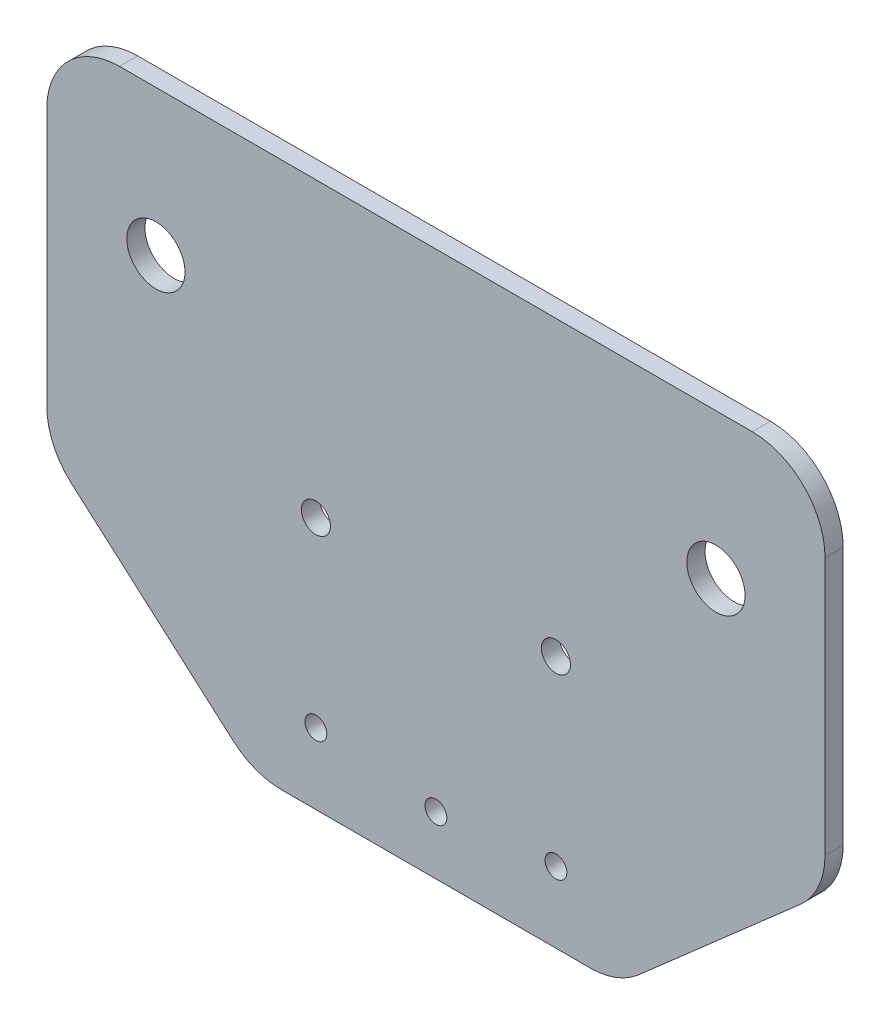
SolidWorks part; units mm, degrees
material "Maple"
ref_plane "Front Plane" through (0, 0, 0) normal (0, 0, 1) x (1, 0, 0)
ref_plane "Top Plane" through (0, 0, 0) normal (0, 1, 0) x (1, 0, 0)
ref_plane "Right Plane" through (0, 0, 0) normal (1, 0, 0) x (0, 0, -1)
sketch "Sketch1" plane through (0, 0, 0) normal (0, 0, 1) x (1, 0, 0)
  line L0 (53.5, 37.5) -> (-53.5, 37.5)
  line L1 (-53.5, -37.5) -> (53.5, -37.5) construction
  line L2 (-53.5, -37.5) -> (-53.5, 37.5) construction
  line L3 (-53.5, 37.5) -> (53.5, 37.5) construction
  line L4 (53.5, -37.5) -> (53.5, 37.5) construction
  line L5 (-53.5, -37.5) -> (53.5, 37.5) construction
  line L6 (-53.5, 37.5) -> (53.5, -37.5) construction
  line L7 (-53.5, 37.5) -> (-53.5, -12.5)
  line L8 (-53.5, -12.5) -> (-25, -37.5)
  line L9 (-25, -37.5) -> (25, -37.5)
  line L10 (0, 37.5) -> (0, -37.5) construction
  line L15 (-26.85, 7.5) -> (13.65, 7.5)
  line L16 (-26.85, 7.5) -> (-26.85, -13)
  line L17 (-26.85, -13) -> (13.65, -13)
  line L18 (13.65, 7.5) -> (13.65, -13)
  line L19 (53.5, -12.5) -> (25, -37.5)
  line L20 (53.5, 37.5) -> (53.5, -12.5)
  line L25 (-26.85, -2.75) -> (13.65, -2.75) construction
  line L26 (-6.6, 7.5) -> (-6.6, -13) construction
  circle A1 centre (0, -29.5) radius 1.5
  circle A2 centre (-16.5, -27.75) radius 1.5
  circle A3 centre (16.5, -27.75) radius 1.5
  circle A5 centre (-38.5, 17.5) radius 4
  circle A6 centre (38.5, 17.5) radius 4
  circle A7 centre (-29.5, 2.25) radius 1.5
  circle A8 centre (-29.5, -7.75) radius 1.5
  circle A9 centre (16.3, 2.25) radius 1.5
  circle A10 centre (16.3, -7.75) radius 1.5
  circle A11 centre (-16.5, -2.75) radius 2
  circle A12 centre (16.5, -2.75) radius 2
  point P0 (0, 0)
  point P29 (-26.85, -2.75)
  dimension "D14" = 3
  dimension "D17" = 10
  dimension "D18" = 45.8
  dimension "D19" = 3
  dimension "D22" = 4
  dimension "D5" = 8
  dimension "D1" = 107
  dimension "D2" = 75
  dimension "D3" = 50
  dimension "D4" = 25
  dimension "D6" = 15
  dimension "D8" = 30
  dimension "D9" = 40.5
  dimension "D10" = 20.5
  dimension "D11" = 10.35
  dimension "D12" = 33
  dimension "D13" = 25
  dimension "D15" = 8
  dimension "D16" = 20
  dimension "D20" = 9.75
  dimension "D21" = 77
extrude "Boss-Extrude1" [suppressed] add sketch "Sketch1" along normal mid plane 2.5
fillet "Fillet1" [suppressed] radius 10
extrude "Boss-Extrude2" add sketch "Sketch1<3>" along normal mid plane 2.5 contours L20 L0 L7 L8 L9 L19 A3 A2 A1 L15 L18 L17 L16 A5 A6 | L18 L15 L16 L17 | A7 | A8 | A10 | A9 region at (52.1933, 12.5, 0) region at (-6.4479, -2.75, 0)
sketch "Sketch1<3>" plane through (0, 0, 0) normal (0, 0, 1) x (1, 0, 0) same geometry as "Sketch1"
fillet "Fillet2" radius 10 6 edges at (53.5, -12.5, 0) (25, -37.5, 0) (-25, -37.5, 0) (-53.5, -12.5, 0) (-53.5, 37.5, 0) (53.5, 37.5, 0)
